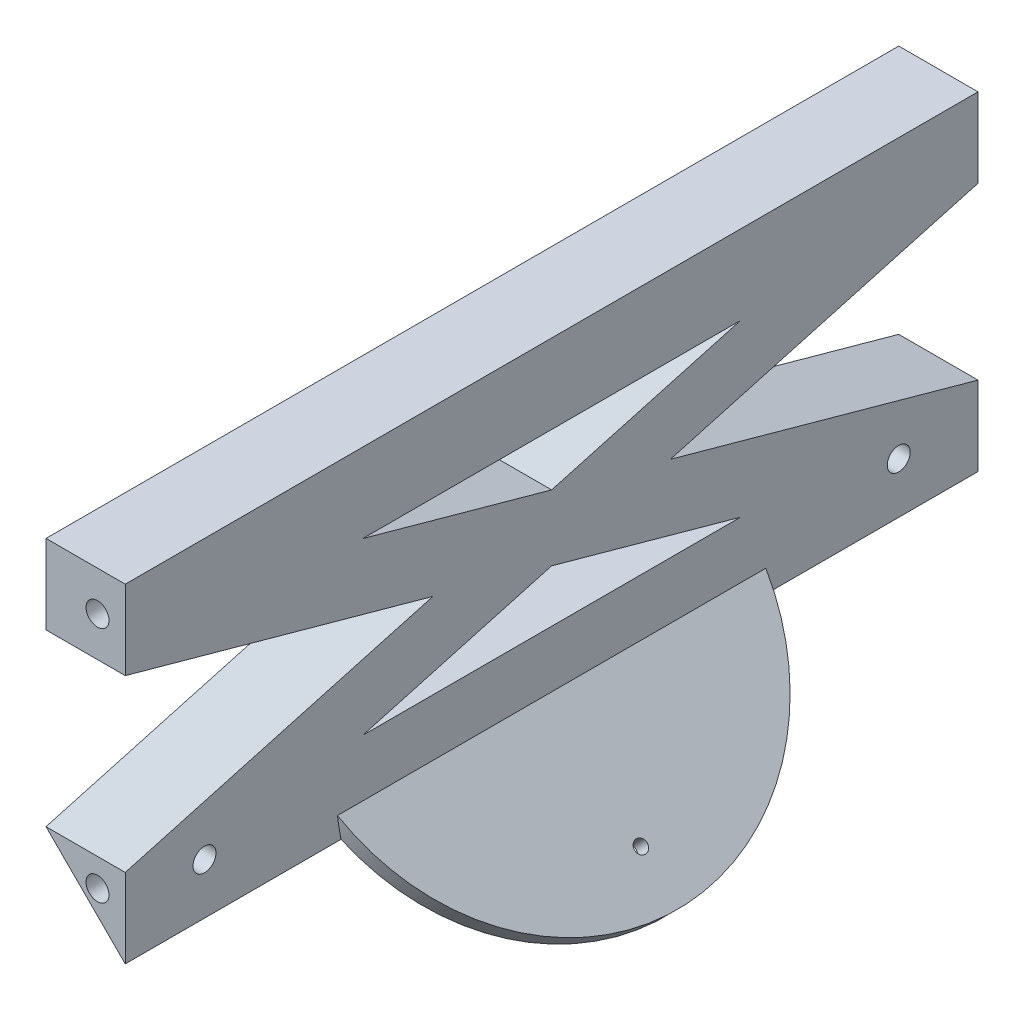
SolidWorks part; units mm, degrees
material "Nylon 101"
ref_plane "Front Plane" through (0, 0, 0) normal (0, 0, 1) x (1, 0, 0)
ref_plane "Top Plane" through (0, 0, 0) normal (0, 1, 0) x (1, 0, 0)
ref_plane "Right Plane" through (0, 0, 0) normal (1, 0, 0) x (0, 0, -1)
sketch "Sketch1" plane through (0, 0, 0) normal (0, 0, 1) x (1, 0, 0)
  line L0 (-7.5, 2.5) -> (2.5, 2.5)
  line L1 (2.5, 2.5) -> (2.5, -7.5)
  line L2 (2.5, -7.5) -> (-7.5, 2.5)
  line L3 (-2.5, -2.5) -> (2.5, 2.5) construction
  dimension "D1" = 10
extrude "Main Body" add sketch "Sketch1" along normal mid plane 107.6
sketch "Sketch4" plane through (-2.5, -2.5, 0) normal (-0.7071, -0.7071, 0) x (0, 0, 1)
  line L0 (0, 7.0711) -> (0, -7.0711) construction
  line L1 (53.8, 7.0711) -> (-53.8, 7.0711) construction
  line L2 (53.8, -7.0711) -> (-53.8, -7.0711) construction
  line L3 (-53.8, 0) -> (53.8, 0) construction
  line L5 (-17.5, 17.5) -> (17.5, 17.5)
  line L6 (-17.5, 17.5) -> (-17.5, -17.5)
  line L7 (-17.5, -17.5) -> (17.5, -17.5)
  line L8 (17.5, 17.5) -> (17.5, -17.5)
  line L9 (-17.5, 17.5) -> (17.5, -17.5) construction
  line L10 (-17.5, -17.5) -> (17.5, 17.5) construction
  circle A0 centre (0, 0) radius 27.5
  point P12 (0, 0)
  line M8 (-53.8, -7.0711) -> (53.8, -7.0711)
  line M10 (53.8, 7.0711) -> (-53.8, 7.0711)
  dimension "D1" = 55
  dimension "D2" = 35
extrude "Boss-Extrude2" add sketch "Sketch4" against normal blind 2 contours L8 L5 L6 M10 | L8 L6 M10 M8 | L8 L6 L7 M8 | A0 L8 L7 L6 M8 | A0 L6 M10 M8 | A0 L6 L5 L8 M10 | A0 L8 M8 M10 region at (-15.4512, 10.4512, 0) region at (-11.1872, 6.1872, 0) region at (-2.5, -2.5, 0) region at (-2.5, -2.5, -22.3508) region at (-2.5, -2.5, 22.3508) region at (6.1872, -11.1872, 0) region at (10.4512, -15.4512, 0)
hole_wizard "M2x0.4 Tapped Hole2" positions "Sketch5" profile "Sketch7" tap size "M2x0.4" standard "ANSI Metric" end condition through all
sketch "Sketch5" plane through (-2.5, -2.5, 0) normal (-0.7071, -0.7071, 0) x (-0.7071, 0.7071, 0)
  line L1 (-17.5, 17.5) -> (-17.5, -17.5) construction
  line L2 (17.5, 17.5) -> (-17.5, 17.5) construction
  line L3 (17.5, -17.5) -> (-17.5, -17.5) construction
  line L4 (7.0711, 0) -> (-7.0711, 0) construction
  line L5 (17.5, 17.5) -> (17.5, -17.5) construction
  point P0 (-21, 0)
  point P2 (14, 21)
  point P4 (14, -21)
  dimension "D1" = 3.5
  dimension "D2" = 3.5
  dimension "D3" = 3.5
  dimension "D4" = 3.5
sketch "Sketch7" plane through (12.3492, -17.3492, 0) normal (0, 0, 1) x (0.7071, -0.7071, 0)
  line L0 (0, 0) -> (0, 29.5)
  line L1 (0, 29.5) -> (0.8, 29.5)
  line L2 (0.8, 29.5) -> (0.8, 0)
  line L5 (0.8, 0) -> (0, 0)
  line L11 (0, -6.35) -> (0, 107.95) construction
  dimension "Thru Tap Drill Dia." = 1.6
  dimension "Thru Tap Drill Depth" = 29.5
cosmetic thread "Hole Thread2" parameters "D2"=2
cosmetic thread "Hole Thread3" parameters "D2"=2
cosmetic thread "Hole Thread4" parameters "D2"=2
hole_wizard "Side holes" positions "Sketch2" profile "Sketch3" hole size "M2.5" standard "ANSI Metric" end condition through all
sketch "Sketch2" plane through (0, 0, 53.8) normal (0, 0, 1) x (1, 0, 0)
  line L0 (-1, 2.5) -> (-1, -1) construction
  line L1 (2.5, 2.5) -> (-7.5, 2.5) construction
  line L2 (-1, -1) -> (2.5, -1) construction
  line L3 (2.5, -7.5) -> (2.5, 2.5) construction
  point P0 (-1, -1)
  point P15 (0, 0)
  point P16 (0, 0)
  dimension "D1" = 3.5
sketch "Sketch3" plane through (-1, -1, 53.8) normal (1, 0, 0) x (0, -1, 0)
  line L0 (0, 0) -> (0, 107.6)
  line L1 (0, 107.6) -> (1.45, 107.6)
  line L2 (1.45, 107.6) -> (1.45, 0)
  line L5 (1.45, 0) -> (0, 0)
  line L11 (0, -6.35) -> (0, 107.95) construction
  dimension "Thru Hole Dia." = 2.9
  dimension "Thru Hole Depth" = 107.6
ref_plane "Plane1" through (0, 0, 0) normal (0.7071, -0.7071, 0) x (0, 0, 1)
sketch "Sketch8" plane through (0, 0, 0) normal (0.7071, -0.7071, 0) x (0, 0, 1)
  line L0 (0, 3.5355) -> (0, 4.5355)
  line L1 (-6.5, 11.0355) -> (-12, 3.5355)
  line L2 (27.5, 3.5355) -> (-27.5, 3.5355) construction
  line L3 (-12, 3.5355) -> (0, 3.5355)
  line L4 (-6.5, 11.0355) -> (0, 11.0355) construction
  line L5 (0, 11.0355) -> (0, 4.5355) construction
  arc A0 (0, 4.5355) -> (-6.5, 11.0355) centre (0, 11.0355) cw
  dimension "D2" = 6.5
  dimension "D1" = 1
  dimension "D3" = 12
revolve "Revolve1" add sketch "Sketch8" angle 360 about L0
fillet "Fillet1" radius 0.5 1 edges at (-12.3995, -3.2071, 0)
sketch "Sketch9" plane through (2.5, 0, 0) normal (1, 0, 0) x (0, 0, -1)
  line L0 (-53.8, -7.5) -> (-53.8, 2.5) construction
  line L1 (-53.8, 34) -> (53.8, 34)
  line L2 (-53.8, 34) -> (-53.8, 24)
  line L3 (-53.8, 24) -> (53.8, 24)
  line L4 (53.8, 34) -> (53.8, 24)
  line L5 (-53.8, 34) -> (53.8, 24) construction
  line L6 (-53.8, 24) -> (53.8, 34) construction
  line L7 (53.8, -7.5) -> (53.8, 2.5) construction
  line L8 (53.8, 2.5) -> (23.8278, 2.5)
  line L9 (-53.8, -7.5) -> (-26.5754, -7.5) construction
  line L10 (53.8, 2.5) -> (-23.8278, 24)
  line L11 (-23.8278, 24) -> (-53.8, 24)
  line L12 (-53.8, 24) -> (23.8278, 2.5)
  line L13 (-53.8, 2.5) -> (53.8, 2.5) construction
  line L14 (-53.8, 2.5) -> (23.8278, 24)
  line L15 (23.8278, 24) -> (53.8, 24)
  line L16 (-23.8278, 2.5) -> (-53.8, 2.5)
  line L17 (-23.8278, 2.5) -> (53.8, 24)
  point P0 (0, 29)
  line M11 (53.8, 2.5) -> (-53.8, 2.5)
  dimension "D1" = 41.5
  dimension "D2" = 10
  dimension "D3" = 8
extrude "Boss-Extrude4" add sketch "Sketch9" against normal up to vertex (10 mm away) contours L4 L1 L2 L3 | L12 L14 L10 L3 | L12 L17 L10 L14 | L10 L17 L3 L14 | L17 L12 L10 M11 | L17 L12 L14 M11 region at (2.5, 29, 0) region at (2.5, 19.5799, 24.0498) region at (2.5, 19.5799, -24.0498) region at (2.5, 13.25, 0) region at (2.5, 6.9201, 24.0498) region at (2.5, 6.9201, -24.0498) up to point (-7.5, 2.5, 53.8)
hole_wizard "M2.5 Clearance Hole1" positions "Sketch10" profile "Sketch11" hole size "M2.5" standard "ANSI Metric" end condition through all
sketch "Sketch10" plane through (0, 0, 53.8) normal (0, 0, 1) x (1, 0, 0)
  line L0 (2.5, 34) -> (2.5, 24) construction
  point P0 (-1, 29)
  point P4 (0, 0)
  point P7 (2.5, 29)
sketch "Sketch11" plane through (-1, 29, 53.8) normal (1, 0, 0) x (0, -1, 0)
  line L0 (0, 0) -> (0, 107.6)
  line L1 (0, 107.6) -> (1.45, 107.6)
  line L2 (1.45, 107.6) -> (1.45, 0)
  line L5 (1.45, 0) -> (0, 0)
  line L11 (0, -6.35) -> (0, 107.95) construction
  dimension "Thru Hole Dia." = 2.9
  dimension "Thru Hole Depth" = 107.6
hole_wizard "M2.5 Clearance Hole2" positions "Sketch12" profile "Sketch13" hole size "M2.5" standard "ANSI Metric" end condition through all
sketch "Sketch12" plane through (2.5, 0, 0) normal (1, 0, 0) x (0, 0, -1)
  line L0 (-53.8, -7.5) -> (-53.8, 2.5) construction
  line L1 (-43.8, -1.0858) -> (43.8, -1.0858) construction
  line L2 (0, -4.6716) -> (0, 2.5) construction
  line L3 (27.0284, -4.6716) -> (-27.0284, -4.6716) construction
  line L5 (-23.8278, 2.5) -> (23.8278, 2.5) construction
  point P0 (-43.8, -1.0858)
  point P2 (43.8, -1.0858)
  point P19 (0, 0)
  point P22 (0, -1.0858)
  point P23 (-59.6984, 6.0266)
  dimension "D1" = 10
sketch "Sketch13" plane through (2.5, -1.0858, 43.8) normal (0, 1, 0) x (0, 0, -1)
  line L0 (0, 0) -> (0, 24.4454)
  line L1 (0, 24.4454) -> (1.45, 24.4454)
  line L2 (1.45, 24.4454) -> (1.45, 0)
  line L5 (1.45, 0) -> (0, 0)
  line L11 (0, -6.35) -> (0, 107.95) construction
  dimension "Thru Hole Dia." = 2.9
  dimension "Thru Hole Depth" = 24.4454
